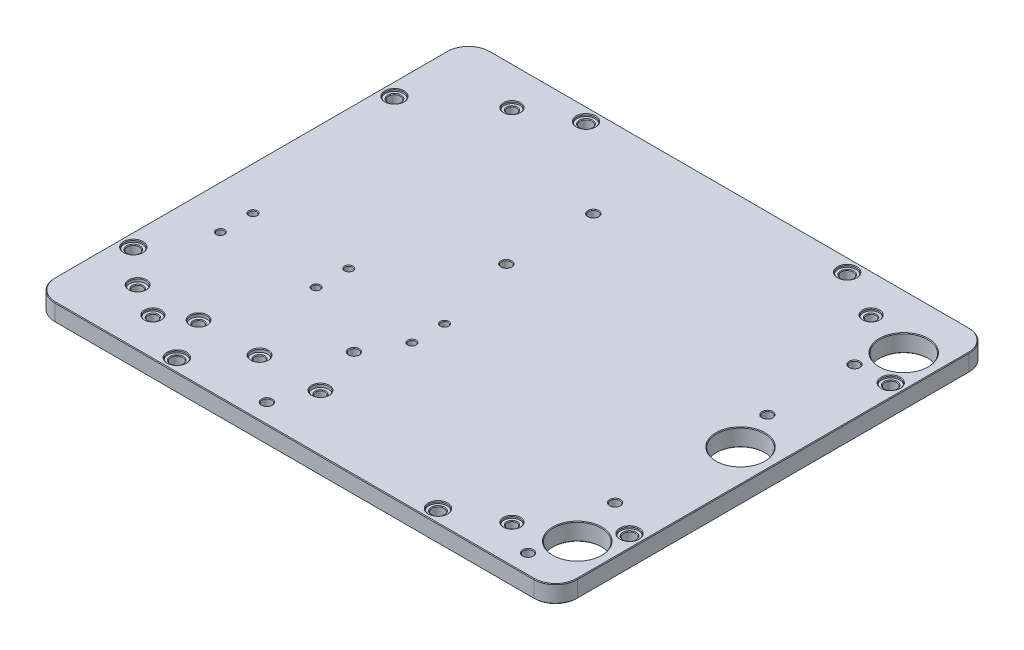
SolidWorks part; units mm, degrees
note: The reader was unsure of these and kept them because the rebuilt part matched: shared geometry of "스케치9<3>", "스케치10<3>", "스케치11<3>".
material "6061-T6 (SS)"
ref_plane "정면" through (0, 0, 0) normal (0, 0, 1) x (1, 0, 0)
ref_plane "윗면" through (0, 0, 0) normal (0, 1, 0) x (1, 0, 0)
ref_plane "우측면" through (0, 0, 0) normal (1, 0, 0) x (0, 0, -1)
sketch "스케치1" plane through (0, 0, 0) normal (0, 1, 0) x (1, 0, 0)
  line L1 (-120, -100) -> (120, -100)
  line L2 (-120, -100) -> (-120, 100)
  line L3 (-120, 100) -> (120, 100)
  line L4 (120, -100) -> (120, 100)
  line L5 (-120, -100) -> (120, 100) construction
  line L6 (-120, 100) -> (120, -100) construction
  point P0 (0, 0)
  dimension "D1" = 200
  dimension "D2" = 240
extrude "보스-돌출1" add sketch "스케치1" along normal blind 8
sketch "스케치2" plane through (0, 0, 0) normal (0, -1, 0) x (1, 0, 0)
  line L0 (-120, 100) -> (120, 100) construction
  line L1 (-105, 77) -> (-7, 77)
  line L2 (-105, 77) -> (-105, 71)
  line L3 (-105, 71) -> (-7, 71)
  line L4 (-7, 77) -> (-7, 71)
  line L5 (-105, 77) -> (-7, 71) construction
  line L6 (-105, 71) -> (-7, 77) construction
  line L7 (-120, -100) -> (-120, 100) construction
  point P0 (-56, 74)
  dimension "D1" = 98
  dimension "D2" = 6
  dimension "D3" = 23
  dimension "D4" = 15
extrude "컷-돌출1" cut sketch "스케치2" against normal blind 2
sketch "스케치3" plane through (0, 2, 0) normal (0, -1, 0) x (1, 0, 0)
  line L0 (-105, 77) -> (-105, 71) construction
  line L1 (-105, 77) -> (-105, 71) construction
  circle A0 centre (-98, 74) radius 2.2
  circle A1 centre (-70, 74) radius 2.2
  circle A2 centre (-42, 74) radius 2.2
  circle A3 centre (-14, 74) radius 2.2
  point P4 (-105, 74)
  dimension "D4" = 4.4
  dimension "D2" = 7
  dimension "D3" = 28
  dimension "D1" = 4
extrude "컷-돌출2" cut sketch "스케치3" against normal blind 10
sketch "스케치4" plane through (0, 0, 0) normal (0, -1, 0) x (1, 0, 0)
  line L0 (-105, 71) -> (-7, 71) construction
  line L1 (-16, 11) -> (-8, 11)
  line L2 (-16, 11) -> (-16, 71)
  line L3 (-16, 71) -> (-8, 71)
  line L4 (-8, 11) -> (-8, 71)
  line L5 (-16, 11) -> (-8, 71) construction
  line L6 (-16, 71) -> (-8, 11) construction
  line L7 (-105, 71) -> (-7, 71) construction
  line L8 (-104, 11) -> (-96, 11)
  line L9 (-104, 11) -> (-104, 71)
  line L10 (-104, 71) -> (-96, 71)
  line L11 (-96, 11) -> (-96, 71)
  line L12 (-104, 11) -> (-96, 71) construction
  line L13 (-104, 71) -> (-96, 11) construction
  line L17 (-7, 77) -> (-105, 77) construction
  line L18 (-60, 11) -> (-52, 11)
  line L19 (-60, 11) -> (-60, 71)
  line L20 (-60, 71) -> (-52, 71)
  line L21 (-52, 11) -> (-52, 71)
  line L22 (-60, 11) -> (-52, 71) construction
  line L23 (-60, 71) -> (-52, 11) construction
  line L25 (-105, 77) -> (-105, 71) construction
  line L26 (-7, 71) -> (-7, 77) construction
  point P0 (-12, 41)
  point P9 (-100, 41)
  point P20 (-56, 41)
  point P28 (-56, 77)
  dimension "D1" = 8
  dimension "D2" = 60
  dimension "D3" = 8
  dimension "D4" = 60
  dimension "D5" = 8
  dimension "D6" = 1
  dimension "D7" = 1
extrude "컷-돌출3" cut sketch "스케치4" against normal blind 1
sketch "스케치5" plane through (0, 1, 0) normal (0, -1, 0) x (1, 0, 0)
  line L0 (-16, 11) -> (-8, 11) construction
  line L1 (-104, 11) -> (-96, 11) construction
  line L2 (-16, 11) -> (-8, 11) construction
  line L3 (-60, 11) -> (-52, 11) construction
  circle A0 centre (-12, 19) radius 1.65
  circle A1 centre (-12, 34) radius 1.65
  circle A2 centre (-100, 34) radius 1.65
  circle A3 centre (-100, 19) radius 1.65
  circle A4 centre (-56, 34) radius 1.65
  circle A5 centre (-56, 19) radius 1.65
  point P14 (-100, 11)
  point P18 (-56, 11)
  point P22 (-12, 11)
  dimension "D1" = 3.3
  dimension "D2" = 8
  dimension "D3" = 15
extrude "컷-돌출4" cut sketch "스케치5" against normal blind 10
sketch "스케치6" plane through (0, 0, 0) normal (0, -1, 0) x (1, 0, 0)
  circle A0 centre (-104, 11) radius 1
  circle A1 centre (-96, 11) radius 1
  circle A2 centre (-60, 11) radius 1
  circle A3 centre (-52, 11) radius 1
  circle A4 centre (-16, 11) radius 1
  circle A5 centre (-8, 11) radius 1
  dimension "D1" = 2
extrude "컷-돌출5" cut sketch "스케치6" against normal blind 1
sketch "스케치7" plane through (0, 0, 0) normal (0, -1, 0) x (1, 0, 0)
  line L0 (-105, 77) -> (-105, 71) construction
  line L1 (-105, 77) -> (-105, 71) construction
  line L2 (-7, 71) -> (-7, 77) construction
  line L3 (-7, 71) -> (-7, 77) construction
  line L4 (-7, 77) -> (-105, 77) construction
  line L5 (-105, 71) -> (-7, 71) construction
  circle A0 centre (-105, 76) radius 1
  circle A1 centre (-105, 72) radius 1
  circle A2 centre (-7, 76) radius 1
  circle A3 centre (-7, 72) radius 1
  dimension "D1" = 2
extrude "컷-돌출6" cut sketch "스케치7" against normal blind 2
sketch "스케치8" plane through (0, 8, 0) normal (0, 1, 0) x (1, 0, 0)
  circle A0 centre (-98, -74) radius 3.75
  circle A1 centre (-70, -74) radius 3.75
  circle A2 centre (-42, -74) radius 3.75
  circle A3 centre (-14, -74) radius 3.75
  dimension "D1" = 7.5
extrude "컷-돌출7" cut sketch "스케치8" against normal blind 1.5
sketch "스케치9" plane through (0, 8, 0) normal (0, 1, 0) x (1, 0, 0)
  line L0 (120, -74) -> (120, -16) construction
  line L1 (120, -100) -> (120, 100) construction
  line L2 (98.37, 59) -> (98.37, -91) construction
  line L3 (120, -100) -> (120, 100) construction
  line L4 (38.37, 59) -> (38.37, -91) construction
  circle A0 centre (98.37, 19) radius 2.2
  circle A1 centre (98.37, -51) radius 2.2
  circle A2 centre (98.37, -91) radius 2.2
  circle A3 centre (98.37, 59) radius 2.2
  circle A4 centre (98.37, 59) radius 4
  circle A5 centre (98.37, 19) radius 4
  circle A6 centre (98.37, -51) radius 4
  circle A7 centre (98.37, -91) radius 4
  circle A8 centre (-21.63, -91) radius 4
  circle A9 centre (-21.63, -91) radius 2.2
  circle A10 centre (-21.63, -51) radius 4
  circle A11 centre (-21.63, -51) radius 2.2
  circle A12 centre (-21.63, 19) radius 4
  circle A13 centre (-21.63, 19) radius 2.2
  circle A14 centre (-21.63, 59) radius 2.2
  circle A15 centre (-21.63, 59) radius 4
  point P9 (0, 0)
  point P13 (98.37, -16)
  point P38 (0, 0)
  point P39 (0, 0)
  dimension "D2" = 4.4
  dimension "D8" = 8
  dimension "D1" = 58
  dimension "D3" = 94.37
  dimension "D4" = 70
  dimension "D5" = 40
  dimension "D6" = 40
  dimension "D7" = 60
extrude "컷-돌출8" cut sketch "스케치9" against normal blind 10 contours A14 | A3 | A0 | A13 | A11 | A1 | A2 | A9
extrude "컷-돌출9" cut sketch "스케치9<3>" against normal blind 10 from offset 5.5 contours A10 A11 | A12 A13 | A15 A14 | A4 A3 | A5 A0 | A6 A1 | A7 A2 | A8 A9 offset against normal yes
sketch "스케치9<3>" plane through (0, 8, 0) normal (0, 1, 0) x (1, 0, 0) same geometry as "스케치9"
sketch "스케치10" plane through (0, 8, 0) normal (0, 1, 0) x (1, 0, 0)
  line L0 (-114, 60) -> (-114, -60) construction
  line L1 (-120, 100) -> (-120, -100) construction
  line L2 (-60, 94) -> (60, 94) construction
  line L3 (120, 100) -> (-120, 100) construction
  line L4 (-120, 0) -> (120, 0) construction
  line L5 (120, -100) -> (120, 100) construction
  line L6 (0, 100) -> (0, -100) construction
  line L7 (-120, -100) -> (120, -100) construction
  circle A0 centre (-114, 60) radius 2.75
  circle A1 centre (-114, -60) radius 2.75
  circle A2 centre (-114, 60) radius 4.5
  circle A3 centre (-114, -60) radius 4.5
  circle A4 centre (-60, 94) radius 2.75
  circle A5 centre (-60, 94) radius 4.5
  circle A6 centre (60, 94) radius 2.75
  circle A7 centre (60, 94) radius 4.5
  circle A8 centre (60, -94) radius 4.5
  circle A9 centre (60, -94) radius 2.75
  circle A10 centre (-60, -94) radius 4.5
  circle A11 centre (-60, -94) radius 2.75
  circle A12 centre (114, -60) radius 4.5
  circle A13 centre (114, -60) radius 2.75
  circle A14 centre (114, 60) radius 4.5
  circle A15 centre (114, 60) radius 2.75
  point P4 (-120, 0)
  point P5 (-114, 0)
  point P14 (0, 100)
  point P15 (0, 94)
  dimension "D3" = 5.5
  dimension "D4" = 9
  dimension "D1" = 120
  dimension "D2" = 6
  dimension "D5" = 6
  dimension "D6" = 120
extrude "컷-돌출10" cut sketch "스케치10" against normal blind 10 contours A0 | A4 | A6 | A15 | A13 | A9 | A1 | A11
extrude "컷-돌출11" cut sketch "스케치10<3>" against normal blind 10 from offset 5.5 contours A2 A0 | A5 A4 | A7 A6 | A14 A15 | A12 A13 | A8 A9 | A3 A1 | A10 A11 offset against normal yes
sketch "스케치10<3>" plane through (0, 8, 0) normal (0, 1, 0) x (1, 0, 0) same geometry as "스케치10"
fillet "필렛1" radius 10 4 edges at (120, 4, 100) (120, 4, -100) (-120, 4, -100) (-120, 4, 100)
sketch "스케치11" plane through (0, 0, 0) normal (0, -1, 0) x (1, 0, 0)
  line L1 (-82.5, -82.5) -> (82.5, -82.5)
  line L2 (-82.5, -82.5) -> (-82.5, 82.5)
  line L3 (-82.5, 82.5) -> (82.5, 82.5)
  line L4 (82.5, -82.5) -> (82.5, 82.5)
  line L5 (-82.5, -82.5) -> (82.5, 82.5) construction
  line L6 (-82.5, 82.5) -> (82.5, -82.5) construction
  circle A0 centre (-82.5, 82.5) radius 2.2
  circle A1 centre (82.5, 82.5) radius 2.2
  circle A2 centre (82.5, -82.5) radius 2.2
  circle A3 centre (-82.5, -82.5) radius 2.2
  circle A4 centre (-82.5, -82.5) radius 4
  circle A5 centre (82.5, -82.5) radius 4
  circle A6 centre (82.5, 82.5) radius 4
  circle A7 centre (-82.5, 82.5) radius 4
  point P0 (0, 0)
  dimension "D1" = 4.4
  dimension "D2" = 8
  dimension "D3" = 165
  dimension "D4" = 165
extrude "컷-돌출12" cut sketch "스케치11" against normal blind 10 contours L3 A0 L2 | L2 A0 L3 | L4 A1 L3 | L3 A1 L4 | L4 A2 L1 | L1 A2 L4 | L2 A3 L1 | L1 A3 L2
extrude "컷-돌출13" cut sketch "스케치11<3>" along normal blind 10 from offset 2.5 contours L3 A7 L2 A0 | L2 A7 L3 A0 | L4 A6 L3 A1 | L3 A6 L4 A1 | L4 A5 L1 A2 | L1 A5 L4 A2 | L1 A4 L2 A3 | L2 A4 L1 A3 offset against normal yes
sketch "스케치11<3>" plane through (0, 0, 0) normal (0, -1, 0) x (1, 0, 0) same geometry as "스케치11"
sketch "스케치12" plane through (0, 8, 0) normal (0, 1, 0) x (1, 0, 0)
  circle A0 centre (-60, 94) radius 4.15
  circle A1 centre (-114, 60) radius 4.15
  circle A2 centre (-114, -60) radius 4.15
  circle A3 centre (-60, -94) radius 4.15
  circle A4 centre (60, -94) radius 4.15
  circle A5 centre (114, -60) radius 4.15
  circle A6 centre (114, 60) radius 4.15
  circle A7 centre (60, 94) radius 4.15
  dimension "D1" = 8.3
extrude "컷-돌출14" cut sketch "스케치12" against normal blind 1
sketch "스케치13" plane through (0, 8, 0) normal (0, 1, 0) x (1, 0, 0)
  circle A0 centre (-82.5, 82.5) radius 3.65
  circle A1 centre (82.5, 82.5) radius 3.65
  circle A2 centre (82.5, -82.5) radius 3.65
  circle A3 centre (-82.5, -82.5) radius 3.65
  dimension "D1" = 7.3
extrude "컷-돌출15" cut sketch "스케치13" against normal blind 1
sketch "스케치14" plane through (0, 8, 0) normal (0, 1, 0) x (1, 0, 0)
  line L0 (105, -75) -> (105, 75) construction
  line L1 (120, -90) -> (120, 90) construction
  circle A0 centre (105, 75) radius 11
  circle A1 centre (105, 0) radius 11
  circle A2 centre (105, -75) radius 11
  point P6 (105, 0)
  point P9 (120, 0)
  point P10 (98.7751, -70.3121)
  point P11 (99.9023, 74.821)
  point P12 (104.4113, -74.821)
  dimension "D1" = 22
  dimension "D2" = 15
  dimension "D3" = 150
extrude "컷-돌출16" cut sketch "스케치14" against normal blind 10
chamfer "모따기1" distance 0.3 angle 45 131 edges at (98.37, 8, 93.2) (98.37, 8, 53.2) (98.37, 8, -16.8) (98.37, 8, -56.8) (-21.63, 8, 93.2) (-21.63, 8, 53.2) (-12, 8, 32.35) (-12, 8, 17.35) (-56, 8, 32.35) (-56, 8, 17.35) (-100, 8, 32.35) (-100, 8, 17.35) (-21.63, 8, -16.8) (-21.63, 8, -56.8) (105, 8, 86) (105, 0, 64) (105, 8, 11) (105, 0, -11) (105, 8, -64) (105, 0, -86) (-14, 2, 71.8) (-42, 2, 71.8) (-70, 2, 71.8) (-98, 2, 71.8) (-100, 1, 32.35) (-100, 1, 17.35) (-56, 1, 32.35) (-56, 1, 17.35) (-12, 1, 32.35) (-12, 1, 17.35) (-100, 1, 71) (-56, 1, 71) (-12, 1, 71) (-7, 0, 74) (-105, 0, 74) (-6, 0, 76) (-106, 0, 76) (-56, 0, 77) (-104, 0, 41.5) (-100, 0, 11) (-96, 0, 41.5) (-78, 0, 71) (-60, 0, 41.5) (-56, 0, 11) (-52, 0, 41.5) (-34, 0, 71) (-16, 0, 41.5) (-8, 0, 41.5) (-12, 0, 11) (-21.63, 0, 47) (-21.63, 2.5, 53.2) (-21.63, 0, -23) (-21.63, 2.5, -16.8) (-21.63, 0, -63) (-21.63, 2.5, -56.8) (-114, 0, 55.5) (-114, 2.5, 62.75) (-82.5, 0, 78.5) (-82.5, 2.5, 80.3) (-60, 0, 89.5) (-60, 2.5, 96.75) (-21.63, 0, 87) (-21.63, 2.5, 93.2) (60, 0, 89.5) (60, 2.5, 96.75) (82.5, 0, 78.5) (82.5, 2.5, 80.3) (98.37, 0, 87) (98.37, 2.5, 93.2) (98.37, 0, 47) (98.37, 2.5, 53.2) (114, 0, 55.5) (114, 2.5, 62.75) (98.37, 0, -23) (98.37, 2.5, -16.8) (98.37, 0, -63) (98.37, 2.5, -56.8) (114, 0, -64.5) (114, 2.5, -57.25) (60, 0, -98.5) (60, 2.5, -91.25) (82.5, 0, -86.5) (82.5, 2.5, -84.7) (-14, 6.5, 76.2) (-14, 8, 77.75) (-42, 8, 77.75) (-42, 6.5, 76.2) (-60, 8, 98.15) (-60, 7, 96.75) (-70, 8, 77.75) (-70, 6.5, 76.2) (-82.5, 7, 84.7) (-82.5, 8, 86.15) (-98, 6.5, 76.2) (-98, 8, 77.75) (-114, 7, 62.75) (-114, 8, 64.15) (82.5, 8, 86.15) (82.5, 7, 84.7) (60, 7, 96.75) (60, 8, 98.15) (114, 7, 62.75) (114, 8, 64.15) (114, 7, -57.25) (114, 8, -55.85) (82.5, 7, -80.3) (82.5, 8, -78.85) (60, 7, -91.25) (60, 8, -89.85) (-60, 8, -89.85) (-60, 7, -91.25) (-82.5, 7, -80.3) (-82.5, 8, -78.85) (-114, 7, -57.25) (-114, 8, -55.85) (-117.0711, 0, 97.0711) (0, 0, 100) (117.0711, 0, 97.0711) (120, 0, 0) (117.0711, 0, -97.0711) (0, 0, -100) (-117.0711, 0, -97.0711) (-120, 0, 0) (-117.0711, 8, -97.0711) (-120, 8, 0) (-117.0711, 8, 97.0711) (0, 8, 100) (117.0711, 8, 97.0711) (120, 8, 0) (117.0711, 8, -97.0711) (0, 8, -100)
